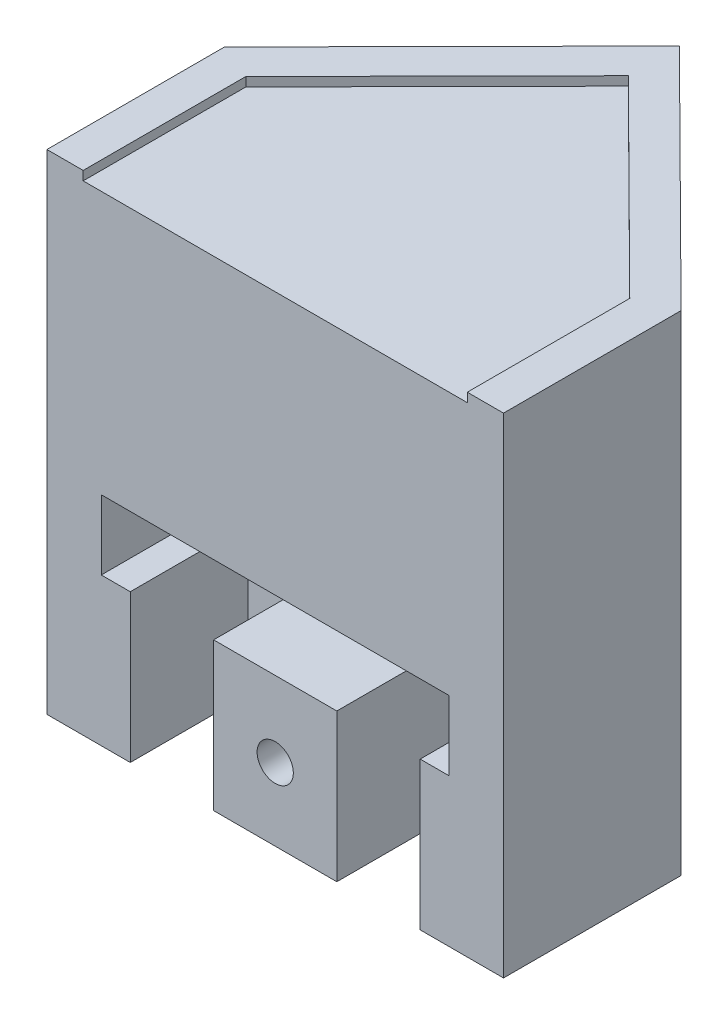
SolidWorks part; units mm, degrees
ref_plane "Plan de face" through (0, 0, 0) normal (0, 0, 1) x (1, 0, 0)
ref_plane "Plan de dessus" through (0, 0, 0) normal (0, 1, 0) x (1, 0, 0)
ref_plane "Plan de droite" through (0, 0, 0) normal (1, 0, 0) x (0, 0, -1)
sketch "Sketch2" plane through (0, 0, 0) normal (0, 0, 1) x (1, 0, 0)
  line L1 (0, 0) -> (-25.2, 0)
  line L2 (0, 0) -> (0, 27)
  line L3 (0, 27) -> (-25.2, 27)
  line L4 (-25.2, 0) -> (-25.2, 27)
  dimension "D1" = 25.2
  dimension "D2" = 27
extrude "Boss-Extrude2" add sketch "Sketch2" along normal blind 2
sketch "Sketch3" plane through (0, 0, 2) normal (0, 0, 1) x (1, 0, 0)
  line L0 (0, 27) -> (-25.2, 27) construction
  line L1 (-25.2, 0) -> (-23.2, 0)
  line L2 (-25.2, 0) -> (-25.2, 27)
  line L3 (-25.2, 27) -> (-23.2, 27)
  line L4 (-23.2, 0) -> (-23.2, 27)
  line L6 (-23.2, 25) -> (0, 25)
  line L7 (-23.2, 25) -> (-23.2, 27)
  line L8 (-23.2, 27) -> (0, 27)
  line L9 (0, 25) -> (0, 27)
  line L10 (0, 0) -> (-2, 0)
  line L11 (0, 0) -> (0, 25)
  line L12 (0, 25) -> (-2, 25)
  line L13 (-2, 0) -> (-2, 25)
  line M4 (0, 0) -> (0, 27)
  line M5 (0, 27) -> (-25.2, 27)
  line M6 (-25.2, 27) -> (-25.2, 0)
  line M7 (-25.2, 0) -> (0, 0)
  dimension "D1" = 2
  dimension "D2" = 2
  dimension "D3" = 2
extrude "Boss-Extrude3" add sketch "Sketch3" along normal blind 7.8 contours L4 M7 M5 M6 | L4 L6 M4 M5 | L13 L6 M7 M4 region at (-24.2, 13.5, 2) region at (-11.6, 26, 2) region at (-1, 12.5, 2)
sketch "Sketch4" plane through (0, 27, 0) normal (0, 1, 0) x (1, 0, 0)
  line L0 (0, 0) -> (-12.6933, 12.5997) construction
  line L1 (-25.2, 0) -> (-12.6933, 12.5997) construction
  line L2 (0, 0) -> (-12.6933, 12.5997)
  line L3 (-12.6933, 12.5997) -> (-25.2, 0)
  line L4 (-25.2, 0) -> (0, 0)
extrude "Boss-Extrude4" add sketch "Sketch4" against normal through all
sketch "Sketch5" plane through (0, 0, 2) normal (0, 0, 1) x (1, 0, 0)
  line L0 (-23.2, 0) -> (-2, 0) construction
  line L1 (-20.85, 0) -> (-4.35, 0)
  line L2 (-20.85, 0) -> (-20.85, 8.1631)
  line L3 (-20.85, 8.1631) -> (-4.35, 8.1631)
  line L4 (-4.35, 0) -> (-4.35, 8.1631)
  line L5 (-20.1, 6) -> (-20.1, 8.5) construction
  line L7 (-2, 0) -> (-2, 25) construction
  line L8 (-23.2, 0) -> (-2, 0)
  line L9 (-23.2, 0) -> (-23.2, 8.1631)
  line L10 (-23.2, 8.1631) -> (-2, 8.1631)
  line L11 (-2, 0) -> (-2, 8.1631)
  line L12 (-17.6, 6) -> (-17.6, 8.5) construction
  line L13 (-15.85, 0) -> (-9.35, 0)
  line L14 (-15.85, 0) -> (-15.85, 8.1631)
  line L15 (-15.85, 8.1631) -> (-9.35, 8.1631)
  line L16 (-9.35, 0) -> (-9.35, 8.1631)
  line M7 (-23.2, 0) -> (-2, 0)
  line M8 (-2, 0) -> (-2, 25)
  line M10 (-23.2, 25) -> (-23.2, 0)
  dimension "D1" = 16.5
  dimension "D2" = 0.75
  dimension "D3" = 0
  dimension "D4" = 6.5
  dimension "D5" = 1.75
extrude "Boss-Extrude5" add sketch "Sketch5" along normal blind 7.8 contours L8 L16 L10 L14 | L10 L4 M7 M8 | L10 L2 M10 M7 region at (-22.025, 4.0815, 2) region at (-12.6, 4.0815, 2) region at (-3.175, 4.0815, 2)
sketch "Sketch6" plane through (0, 0, 2) normal (0, 0, 1) x (1, 0, 0)
  line L1 (-20.85, 0) -> (-15.85, 0)
  line L2 (-20.85, 0) -> (-20.85, 8.1631)
  line L3 (-20.85, 8.1631) -> (-15.85, 8.1631)
  line L4 (-15.85, 0) -> (-15.85, 8.1631)
  line L5 (-9.35, 0) -> (-4.35, 0)
  line L6 (-9.35, 0) -> (-9.35, 8.1631)
  line L7 (-9.35, 8.1631) -> (-4.35, 8.1631)
  line L8 (-4.35, 0) -> (-4.35, 8.1631)
extrude "Boss-Extrude6" add sketch "Sketch6" along normal blind 1.3
sketch "Sketch8" plane through (0, 27, 0) normal (0, 1, 0) x (1, 0, 0)
  line L6 (-23.2, -7.8) -> (-2, -7.8)
  line L7 (-23.2, -7.8) -> (-23.2, -9.8)
  line L8 (-23.2, -9.8) -> (-2, -9.8)
  line L9 (-2, -7.8) -> (-2, -9.8)
  line L10 (-2, -7.8) -> (-2, -0.8328)
  line L11 (-2, -0.8328) -> (-12.6829, 9.7712)
  line L12 (-12.6829, 9.7712) -> (-23.2, -0.8241)
  line L13 (-23.2, -0.8241) -> (-23.2, -7.8)
  line L14 (-23.2, -7.8) -> (-2, -7.8)
  line L15 (-2, -7.8) -> (-2, -0.8328)
  line L16 (-2, -0.8328) -> (-12.6829, 9.7712)
  line L17 (-12.6829, 9.7712) -> (-23.2, -0.8241)
  line L18 (-23.2, -0.8241) -> (-23.2, -7.8)
  line L19 (-23.2, -7.8) -> (-2, -7.8)
  line M10 (-25.2, -9.8) -> (0, -9.8)
  dimension "D1" = 2
extrude "Cut-Extrude1" cut sketch "Sketch8" against normal blind 0.5 contours L17 L18 L6 L15 L16 | L9 L6 L7 M10 region at (-12.6132, 27, 1.2828) region at (-12.6, 27, 8.8)
sketch "Sketch10" plane through (0, 0, 9.8) normal (0, 0, 1) x (1, 0, 0)
  circle A0 centre (-12.6, 4) radius 1
extrude "Cut-Extrude4" cut sketch "Sketch10" along direction (0, 0, 1) on the side against the normal blind 6
sketch "Sketch11" plane through (0, 25, 0) normal (0, -1, 0) x (1, 0, 0)
  line L1 (-23.2, 2) -> (-2, 2)
  line L2 (-23.2, 2) -> (-23.2, 9.8)
  line L3 (-23.2, 9.8) -> (-2, 9.8)
  line L4 (-2, 2) -> (-2, 9.8)
extrude "Boss-Extrude7" add sketch "Sketch11" along normal blind 1
sketch "Sketch12" plane through (0, 0, 2) normal (0, 0, 1) x (1, 0, 0)
  line L1 (-23.2, 24) -> (-2, 24)
  line L2 (-23.2, 24) -> (-23.2, 8.1631)
  line L3 (-23.2, 8.1631) -> (-2, 8.1631)
  line L4 (-2, 24) -> (-2, 8.1631)
extrude "Boss-Extrude8" add sketch "Sketch12" along normal blind 1.05
sketch "Sketch13" plane through (-20.85, 0, 0) normal (1, 0, 0) x (0, 0, -1)
  line L1 (-3.3, 8.1631) -> (-9.8, 8.1631)
  line L2 (-3.3, 8.1631) -> (-3.3, 0)
  line L3 (-3.3, 0) -> (-9.8, 0)
  line L4 (-9.8, 8.1631) -> (-9.8, 0)
extrude "Boss-Extrude9" add sketch "Sketch13" along normal blind 0.25
sketch "Sketch14" plane through (-4.35, 0, 0) normal (-1, 0, 0) x (0, 0, 1)
  line L1 (3.3, 8.1631) -> (9.8, 8.1631)
  line L2 (3.3, 8.1631) -> (3.3, 0)
  line L3 (3.3, 0) -> (9.8, 0)
  line L4 (9.8, 8.1631) -> (9.8, 0)
extrude "Boss-Extrude11" add sketch "Sketch14" along normal blind 0.25
sketch "Sketch15" plane through (-9.35, 0, 0) normal (1, 0, 0) x (0, 0, -1)
  line L1 (-3.3, 8.1631) -> (-9.8, 8.1631)
  line L2 (-3.3, 8.1631) -> (-3.3, 0)
  line L3 (-3.3, 0) -> (-9.8, 0)
  line L4 (-9.8, 8.1631) -> (-9.8, 0)
extrude "Boss-Extrude12" add sketch "Sketch15" along normal blind 0.15
sketch "Sketch16" plane through (-15.85, 0, 0) normal (-1, 0, 0) x (0, 0, 1)
  line L1 (3.3, 8.1631) -> (9.8, 8.1631)
  line L2 (3.3, 8.1631) -> (3.3, 0)
  line L3 (3.3, 0) -> (9.8, 0)
  line L4 (9.8, 8.1631) -> (9.8, 0)
extrude "Boss-Extrude13" add sketch "Sketch16" along normal blind 0.15
sketch "Sketch17" plane through (-23.2, 0, 0) normal (1, 0, 0) x (0, 0, -1)
  line L1 (-3.05, 24) -> (-9.8, 24)
  line L2 (-3.05, 24) -> (-3.05, 8.1631)
  line L3 (-3.05, 8.1631) -> (-9.8, 8.1631)
  line L4 (-9.8, 24) -> (-9.8, 8.1631)
extrude "Boss-Extrude14" add sketch "Sketch17" along normal blind 1
sketch "Sketch18" plane through (-2, 0, 0) normal (-1, 0, 0) x (0, 0, 1)
  line L1 (3.05, 24) -> (9.8, 24)
  line L2 (3.05, 24) -> (3.05, 8.1631)
  line L3 (3.05, 8.1631) -> (9.8, 8.1631)
  line L4 (9.8, 24) -> (9.8, 8.1631)
extrude "Boss-Extrude15" add sketch "Sketch18" along normal blind 1
sketch "Sketch19" plane through (0, 24, 0) normal (0, -1, 0) x (1, 0, 0)
  line L1 (-22.2, 3.05) -> (-3, 3.05)
  line L2 (-22.2, 3.05) -> (-22.2, 9.8)
  line L3 (-22.2, 9.8) -> (-3, 9.8)
  line L4 (-3, 3.05) -> (-3, 9.8)
extrude "Boss-Extrude16" add sketch "Sketch19" along normal blind 12
